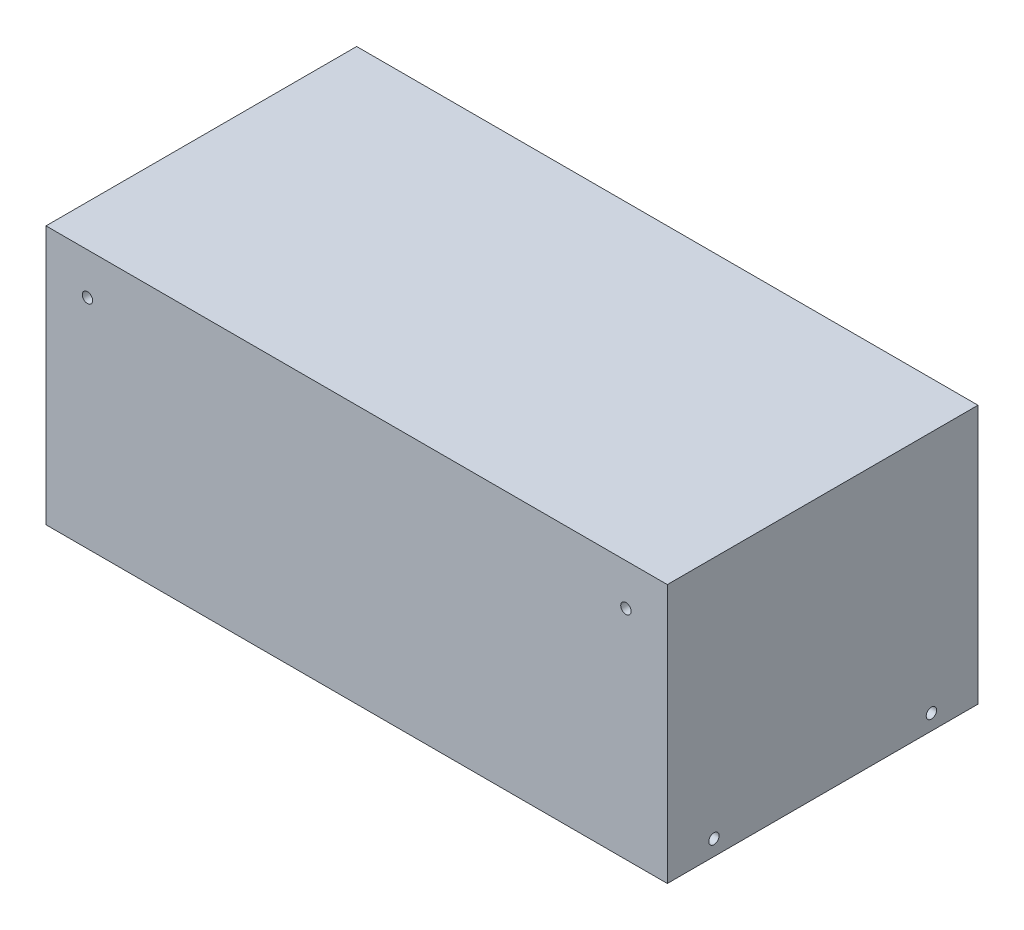
SolidWorks part; units mm, degrees
material "ABS PC"
ref_plane "Front Plane" through (0, 0, 0) normal (0, 0, 1) x (1, 0, 0)
ref_plane "Top Plane" through (0, 0, 0) normal (0, 1, 0) x (1, 0, 0)
ref_plane "Right Plane" through (0, 0, 0) normal (1, 0, 0) x (0, 0, -1)
sketch "Sketch1" plane through (0, 0, 0) normal (0, 1, 0) x (1, 0, 0)
  line L1 (150, -75) -> (-150, -75)
  line L2 (150, -75) -> (150, 75)
  line L3 (150, 75) -> (-150, 75)
  line L4 (-150, -75) -> (-150, 75)
  line L5 (150, -75) -> (-150, 75) construction
  line L6 (150, 75) -> (-150, -75) construction
  point P0 (0, 0)
  dimension "D1" = 300
  dimension "D2" = 150
extrude "Boss-Extrude1" add sketch "Sketch1" along normal blind 125
sketch "Sketch2" plane through (0, 0, 0) normal (0, -1, 0) x (1, 0, 0)
  line L0 (-150, 75) -> (150, 75) construction
  line L1 (135, -60) -> (-135, -60)
  line L2 (135, -60) -> (135, 60)
  line L3 (135, 60) -> (-135, 60)
  line L4 (-135, -60) -> (-135, 60)
  line L5 (135, -60) -> (-135, 60) construction
  line L6 (135, 60) -> (-135, -60) construction
  line L7 (150, 75) -> (150, -75) construction
  point P0 (0, 0)
  point P8 (150, 0)
  dimension "D1" = 15
  dimension "D2" = 15
extrude "Cut-Extrude1" cut sketch "Sketch2" against normal blind 110
sketch "Sketch4" plane through (150, 0, 0) normal (1, 0, 0) x (0, 0, -1)
  line L0 (-75, 0) -> (75, 0) construction
  line L1 (75, 125) -> (75, 0) construction
  line L5 (-75, 125) -> (-75, 0) construction
  circle A0 centre (-52.5, 7.5) radius 2.5
  circle A1 centre (52.5, 7.5) radius 2.5
  dimension "D3" = 5
  dimension "D4" = 5
  dimension "D1" = 7.5
  dimension "D2" = 22.5
  dimension "D5" = 7.5
  dimension "D6" = 22.5
extrude "Cut-Extrude5" cut sketch "Sketch4" against normal blind 350
sketch "Sketch6" plane through (0, 0, 75) normal (0, 0, 1) x (1, 0, 0)
  line L0 (-150, 125) -> (-150, 0) construction
  line L1 (-150, 125) -> (150, 125) construction
  line L2 (0, 140.9499) -> (0, -14.4188) construction
  circle A0 centre (-130, 105) radius 2.5
  circle A1 centre (130, 105) radius 2.5
  dimension "D1" = 5
  dimension "D2" = 20
  dimension "D3" = 20
extrude "Cut-Extrude6" cut sketch "Sketch6" against normal blind 175
